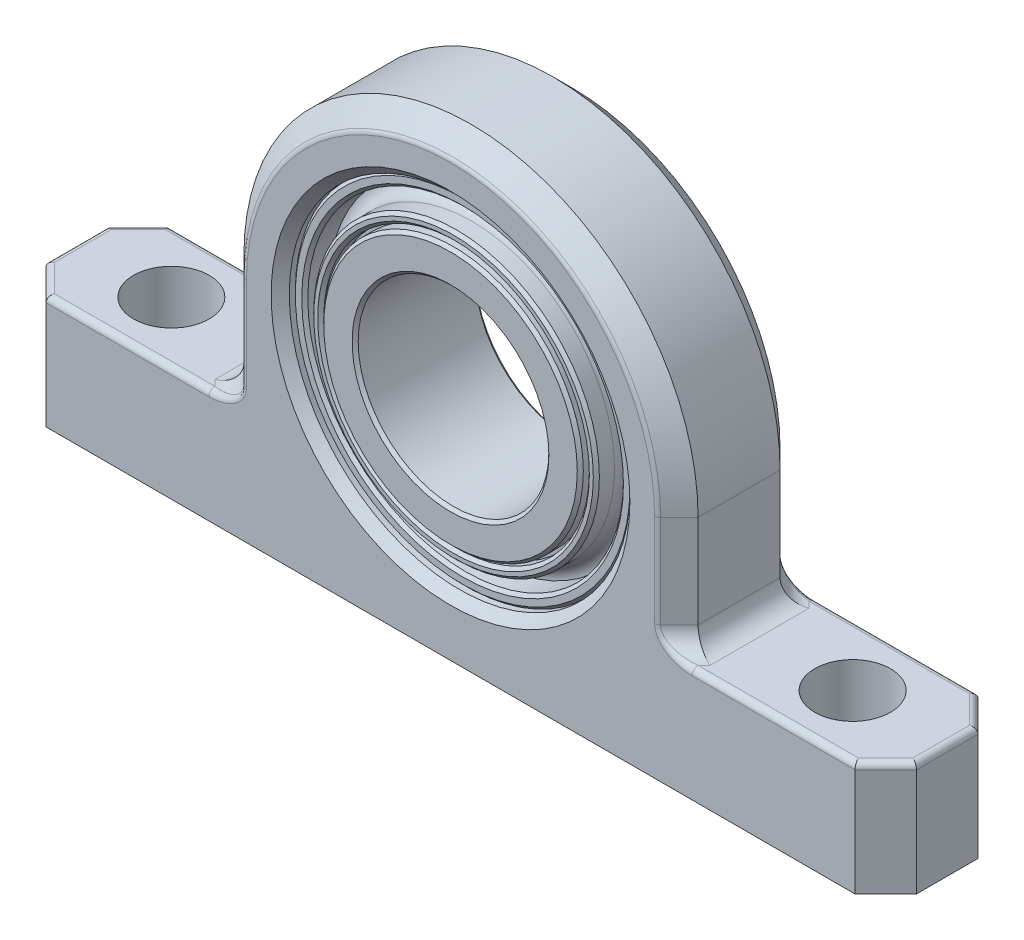
SolidWorks part; units mm, degrees
ref_plane "Front Plane" through (0, 0, 0) normal (0, 0, 1) x (1, 0, 0)
ref_plane "Top Plane" through (0, 0, 0) normal (0, 1, 0) x (1, 0, 0)
ref_plane "Right Plane" through (0, 0, 0) normal (1, 0, 0) x (0, 0, -1)
sketch "Sketch1" plane through (0, 0, 0) normal (0, 0, 1) x (1, 0, 0)
  line L0 (9.525, 0) -> (9.525, -4.7625)
  line L1 (9.525, -4.7625) -> (18.2562, -4.7625)
  line L2 (18.2562, -4.7625) -> (18.2562, -9.525)
  line L3 (18.2562, -9.525) -> (-18.2563, -9.525)
  line L4 (-18.2563, -9.525) -> (-18.2563, -4.7625)
  line L5 (-18.2563, -4.7625) -> (-9.525, -4.7625)
  line L6 (-9.525, -4.7625) -> (-9.525, 0)
  circle A0 centre (0, 0) radius 4
  arc A1 (9.525, 0) -> (-9.525, 0) centre (0, 0) ccw
  circle A2 centre (0, 0) radius 7.1438
  point P12 (0, 7.1437)
  point P13 (0, 4)
  dimension "shaft dia" = 8
  dimension "D1" = 14.2875
sketch "Sketch2" plane through (0, 0, 0) normal (0, 1, 0) x (1, 0, 0)
  line L0 (0, 2.5797) -> (0, -2.5797) construction
  line L1 (-14.2875, 0) -> (14.2875, 0) construction
  circle A0 centre (14.2875, 0) radius 1.5875
  circle A1 centre (-14.2875, 0) radius 1.5875
  dimension "Overall Width" = 5.1594
sketch "Sketch3" plane through (0, 0, 0) normal (0, 0, 1) x (1, 0, 0)
  line L0 (9.525, 0) -> (9.525, -4.7625) construction
  line L1 (18.2562, -4.7625) -> (18.2562, -9.525) construction
  line L2 (9.525, -4.7625) -> (18.2562, -4.7625) construction
  line L3 (18.2562, -9.525) -> (-18.2563, -9.525) construction
  line L4 (-18.2563, -9.525) -> (-18.2563, -4.7625) construction
  line L5 (-18.2563, -4.7625) -> (-9.525, -4.7625) construction
  line L6 (-9.525, -4.7625) -> (-9.525, 0) construction
  line L7 (9.525, 0) -> (9.525, -4.7625)
  line L8 (18.2562, -4.7625) -> (18.2562, -9.525)
  line L9 (9.525, -4.7625) -> (18.2562, -4.7625)
  line L10 (18.2562, -9.525) -> (-18.2563, -9.525)
  line L11 (-18.2563, -9.525) -> (-18.2563, -4.7625)
  line L12 (-18.2563, -4.7625) -> (-9.525, -4.7625)
  line L13 (-9.525, -4.7625) -> (-9.525, 0)
  arc A0 (9.525, 0) -> (-9.525, 0) centre (0, 0) ccw construction
  circle A1 centre (0, 0) radius 7.1438 construction
  arc A2 (9.525, 0) -> (-9.525, 0) centre (0, 0) ccw
  circle A3 centre (0, 0) radius 7.1438
extrude "Extrude1" add sketch "Sketch3" along normal up to vertex (2.5797 mm away) and the other way up to vertex (2.5797 mm away) up to point (0, 0, 2.5797) other way up to point (0, 0, -2.5797)
sketch "Sketch4" plane through (0, -4.7625, 0) normal (0, 1, 0) x (1, 0, 0)
  line L0 (-18.2563, 2.5797) -> (-18.2563, 1.2898)
  line L1 (-18.2563, -2.5797) -> (-18.2563, 2.5797) construction
  line L2 (-18.2563, 1.2898) -> (-16.9664, 2.5797)
  line L3 (-9.525, 2.5797) -> (-18.2563, 2.5797) construction
  line L4 (-16.9664, 2.5797) -> (-18.2563, 2.5797)
  line L5 (0, 0) -> (0, 2.5797) construction
  line L6 (0, 0) -> (-14.2875, 0) construction
  line L7 (16.9664, 2.5797) -> (18.2563, 2.5797)
  line L8 (18.2563, 1.2898) -> (16.9664, 2.5797)
  line L9 (18.2563, 2.5797) -> (18.2563, 1.2898)
  line L10 (18.2563, -2.5797) -> (18.2563, -1.2898)
  line L11 (18.2563, -1.2898) -> (16.9664, -2.5797)
  line L12 (16.9664, -2.5797) -> (18.2563, -2.5797)
  line L13 (-16.9664, -2.5797) -> (-18.2563, -2.5797)
  line L14 (-18.2563, -1.2898) -> (-16.9664, -2.5797)
  line L15 (-18.2563, -2.5797) -> (-18.2563, -1.2898)
  circle A0 centre (-14.2875, 0) radius 1.5875 construction
  circle A1 centre (14.2875, 0) radius 1.5875 construction
  circle A2 centre (-14.2875, 0) radius 1.5875
  circle A3 centre (14.2875, 0) radius 1.5875
  dimension "D1" = 45
  dimension "D2" = 1.2898
extrude "Cut-Extrude1" cut sketch "Sketch4" against normal through all
chamfer "Chamfer3" distance 0.8599 angle 45 6 edges at (-9.525, -2.3812, -2.5797) (0, 9.525, -2.5797) (9.525, -2.3812, -2.5797) (-9.525, -2.3812, 2.5797) (0, 9.525, 2.5797) (9.525, -2.3812, 2.5797)
fillet "Fillet6" radius 0.8599 6 edges at (9.525, -4.7625, 0) (9.0951, -4.7625, -2.1497) (9.0951, -4.7625, 2.1497) (-9.0951, -4.7625, -2.1497) (-9.0951, -4.7625, 2.1497) (-9.525, -4.7625, 0)
fillet "Fillet7" radius 0.254 20 edges at (13.4238, -4.7625, -2.5797) (9.0213, -4.5106, -2.5797) (8.6651, -1.9513, -2.5797) (0, 8.6651, -2.5797) (-8.6651, -1.9513, -2.5797) (-9.0213, -4.5106, -2.5797) (13.4238, -4.7625, 2.5797) (9.0213, -4.5106, 2.5797) (8.6651, -1.9513, 2.5797) (0, 8.6651, 2.5797) (-8.6651, -1.9513, 2.5797) (-9.0213, -4.5106, 2.5797) (17.6113, -4.7625, 1.9348) (18.2562, -4.7625, 0) (17.6113, -4.7625, -1.9348) (-13.4238, -4.7625, -2.5797) (-17.6113, -4.7625, -1.9348) (-18.2563, -4.7625, 0) (-17.6113, -4.7625, 1.9348) (-13.4238, -4.7625, 2.5797)
chamfer "Chamfer4" distance 0.381 angle 45 2 edges at (7.1438, 0, -2.5797) (7.1438, 0, 2.5797)
sketch "Sketch5" plane through (0, 0, 0) normal (1, 0, 0) x (0, 0, -1)
  line L0 (-2.0717, 6.6198) -> (-1.0557, 6.6198)
  line L1 (0, 7.1437) -> (0, 4) construction
  line L2 (2.0717, 7.1437) -> (2.0717, 6.6198)
  line L4 (2.0717, 6.6198) -> (1.0557, 6.6198)
  line L5 (-1.0557, 6.6198) -> (-1.0557, 5.991)
  line L6 (-1.0557, 5.991) -> (-2.4527, 5.991)
  line L7 (-1.9447, 5.4449) -> (-1.9447, 5.5719)
  line L8 (-2.5797, 4) -> (2.5797, 4)
  line L9 (-1.9447, 5.4449) -> (-2.5797, 5.4449)
  line L10 (-2.0717, 7.1437) -> (2.0717, 7.1437)
  line L11 (1.0557, 6.6198) -> (1.0557, 5.991)
  line L12 (-2.5797, 5.4449) -> (-2.5797, 4)
  line L13 (-2.0717, 7.1437) -> (-2.0717, 6.6198)
  line L15 (-1.9447, 5.5719) -> (-2.4527, 5.5719)
  line L16 (-2.4527, 5.5719) -> (-2.4527, 5.991)
  line L17 (0, 7.1437) -> (0, 9.525) construction
  line L18 (0, 9.525) -> (0, 0) construction
  line L19 (1.0557, 5.991) -> (2.4527, 5.991)
  line L20 (2.4527, 5.5719) -> (2.4527, 5.991)
  line L21 (1.9447, 5.5719) -> (2.4527, 5.5719)
  line L22 (1.9447, 5.4449) -> (1.9447, 5.5719)
  line L23 (1.9447, 5.4449) -> (2.5797, 5.4449)
  line L24 (2.5797, 5.4449) -> (2.5797, 4)
  line L27 (1.7198, 9.525) -> (-1.7198, 9.525) construction
  point P9 (0, 5.5719)
  dimension "D1" = 3.1437
  dimension "D2" = 0.524
  dimension "D3" = 0.6287
  dimension "D6" = 1.016
  dimension "D5" = 0.635
  dimension "D7" = 0.127
  dimension "D8" = 0.127
  dimension "D9" = 0.508
revolve "Revolve1" add sketch "Sketch5" angle 360 about L0
chamfer "Chamfer5" distance 0.127 angle 45 12 edges at (-5.4449, 0, 2.5797) (-4, 0, 2.5797) (-5.991, 0, 2.4527) (-5.5719, 0, 2.4527) (-7.1437, 0, 2.0717) (-6.6198, 0, 2.0717) (-4, 0, -2.5797) (-5.4449, 0, -2.5797) (-5.5719, 0, -2.4527) (-5.991, 0, -2.4527) (-6.6198, 0, -2.0717) (-7.1437, 0, -2.0717)
fillet "Fillet8" radius 0.635 2 edges at (-5.991, 0, 1.0557) (-5.991, 0, -1.0557)
equation "\"D1@Sketch1\"=\"I@Sketch1\"*.75"
equation "\"D2@Sketch4\" = \"Overall Width@Sketch2\" / 4"
equation "\"D1@Chamfer3\" = \"Overall Width@Sketch2\" / 6"
equation "\"D1@Fillet6\"=\"D1@Chamfer3\""
equation "\"D2@Sketch5\"=\"D1@Sketch5\"/6"
equation "\"D3@Sketch5\"=\"D2@Sketch5\"*1.2"
